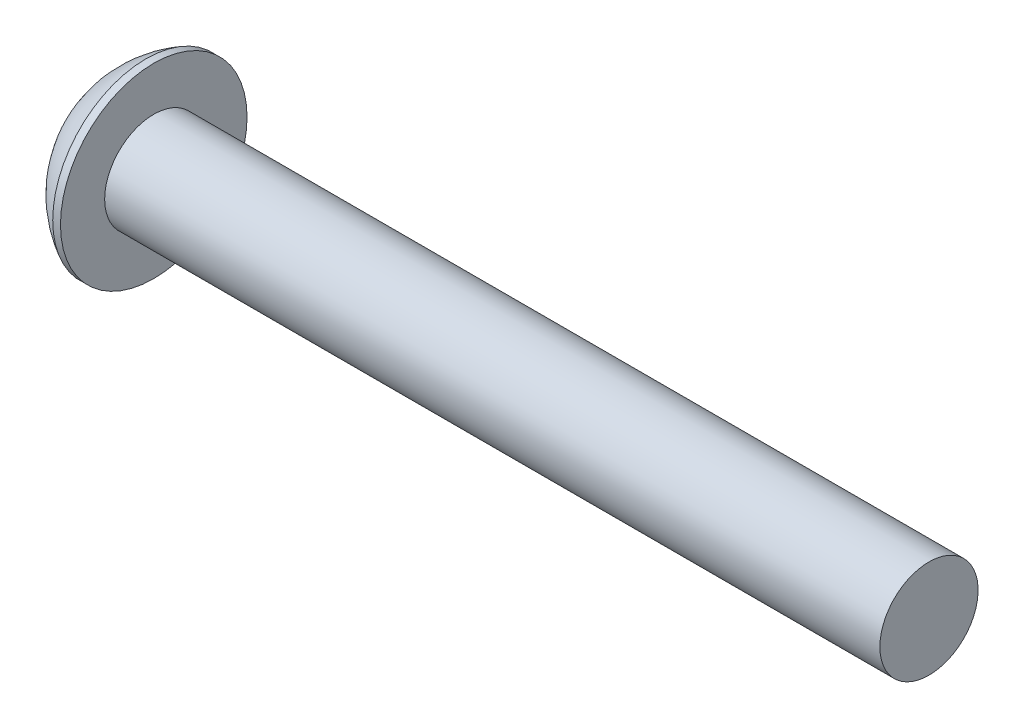
SolidWorks part; units mm, degrees
material "Alloy Steel"
ref_plane "Front" through (0, 0, 0) normal (0, 0, 1) x (1, 0, 0)
ref_plane "Top" through (0, 0, 0) normal (0, 1, 0) x (1, 0, 0)
ref_plane "Right" through (0, 0, 0) normal (1, 0, 0) x (0, 0, -1)
sketch "Sketch1" plane through (0, 0, 0) normal (0, 0, 1) x (1, 0, 0)
  line L0 (0, 0) -> (38.8366, 0)
  line L1 (38.8366, 0) -> (38.8366, 2.413)
  line L2 (38.8366, 2.413) -> (0.7366, 2.413)
  line L3 (0.7366, 2.413) -> (0.7366, 4.5847)
  line L4 (0.7366, 4.5847) -> (0.3556, 4.5847)
  line L5 (-1.8288, 2.413) -> (-1.8288, 1.8288)
  line L6 (0, 0) -> (4.2959, 0) construction
  line L7 (-1.8288, 1.8288) -> (0, 0)
  arc A0 (-1.8288, 2.413) -> (0.3556, 4.5847) centre (2.7515, -0.0097) cw
  dimension "Head Radius" = 5.1816
  dimension "Edge Flat" = 0.381
  dimension "Thread Length" = 38.1
  dimension "Head Diameter" = 9.1694
  dimension "Thread Diameter" = 4.826
  dimension "D6" = 45
  dimension "Head Height" = 2.5654
  dimension "Hex Chamfer Radius" = 1.8288
revolve "Revolve1" add sketch "Sketch1" angle 360 about L6
sketch "Sketch2" plane through (-1.8288, 0, 0) normal (-1, 0, 0) x (0, 0, 1)
  line L1 (1.8331, 0) -> (0.9165, 1.5875)
  line L2 (0.9165, 1.5875) -> (-0.9165, 1.5875)
  line L3 (-0.9165, 1.5875) -> (-1.8331, 0)
  line L4 (-1.8331, 0) -> (-0.9165, -1.5875)
  line L5 (-0.9165, -1.5875) -> (0.9165, -1.5875)
  line L6 (0.9165, -1.5875) -> (1.8331, 0)
  circle A0 centre (0, 0) radius 1.5875 construction
  dimension "Hex Width" = 3.175
extrude "Cut-Extrude1" cut sketch "Sketch2" against normal up to vertex (1.8288 mm away) up to point (0, 0, 0)
other "Freeze***"
